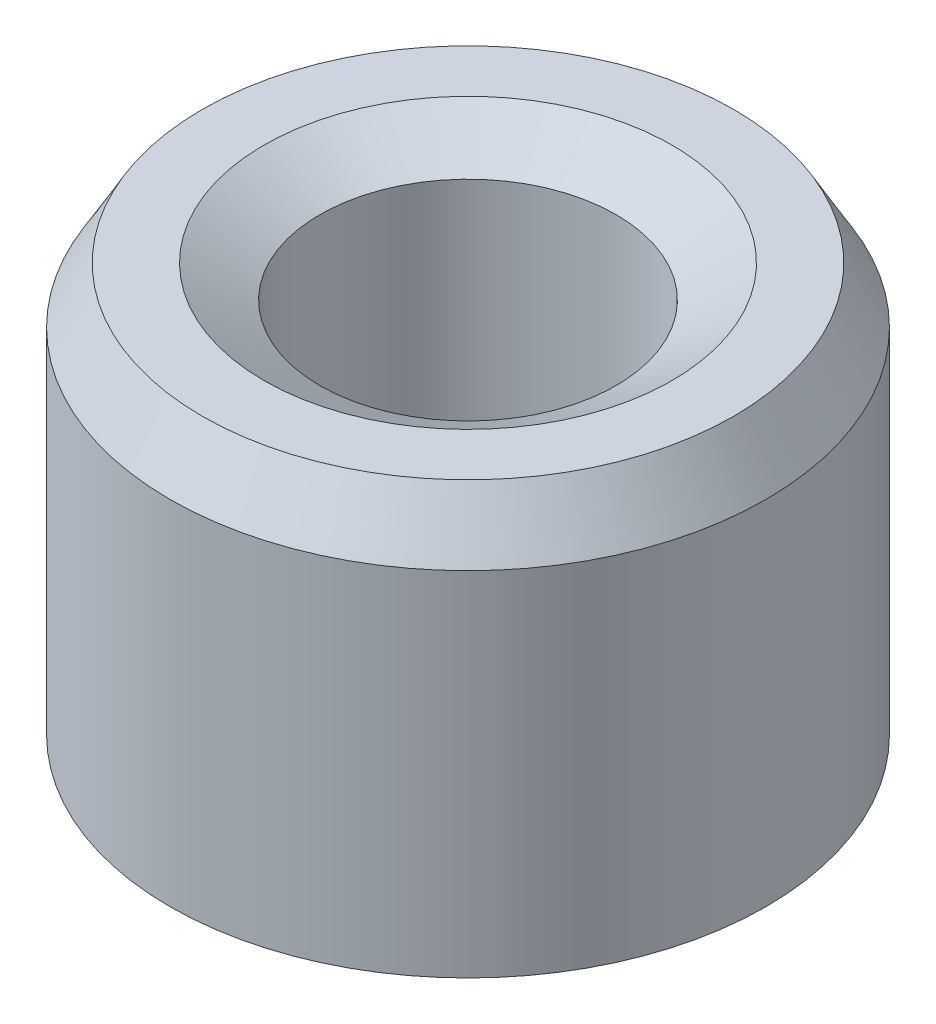
SolidWorks part; units mm, degrees
ref_plane "Front Plane" through (0, 0, 0) normal (0, 0, 1) x (1, 0, 0)
ref_plane "Top Plane" through (0, 0, 0) normal (0, 1, 0) x (1, 0, 0)
ref_plane "Right Plane" through (0, 0, 0) normal (1, 0, 0) x (0, 0, -1)
sketch "Sketch1" plane through (0, 0, 0) normal (0, 1, 0) x (1, 0, 0)
  circle A0 centre (0, 0) radius 10
  dimension "SLEEVE_OD" = 20
extrude "Boss-Extrude1" add sketch "Sketch1" along normal blind 14.7944
sketch "Sketch2" plane through (0, 0, 0) normal (0, 1, 0) x (1, 0, 0)
  circle A0 centre (0, 0) radius 4.9698
  dimension "BORE_D" = 9.9395
extrude "Cut-Extrude1" cut sketch "Sketch2" along normal through all
chamfer "Chamfer1" distance 1.8757 angle 30 4 edges at (0, 14.7944, 4.9698) (0, 0, 4.9698) (0, 0, 10) (0, 14.7944, 10) first distance on face at (0, 14.7944, 4.9698) first distance on face at (0, 0, 4.9698) first distance on face at (0, 14.7944, 10)
